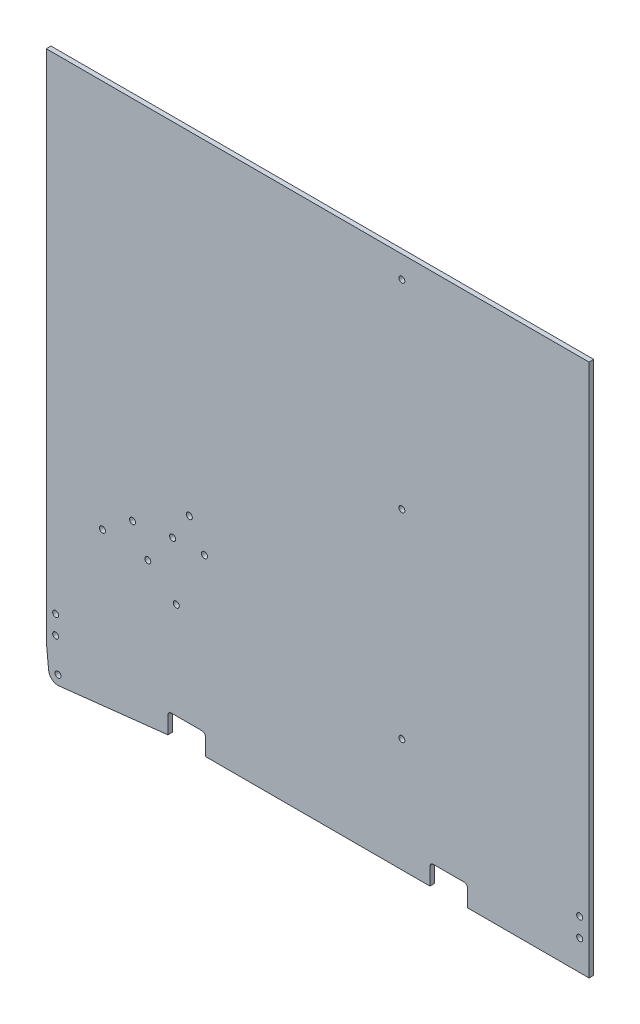
SolidWorks part; units mm, degrees
ref_plane "Front Plane" through (0, 0, 0) normal (0, 0, 1) x (1, 0, 0)
ref_plane "Top Plane" through (0, 0, 0) normal (0, 1, 0) x (1, 0, 0)
ref_plane "Right Plane" through (0, 0, 0) normal (1, 0, 0) x (0, 0, -1)
sketch "Sketch1" plane through (0, 0, 0) normal (0, 0, 1) x (1, 0, 0)
  line L0 (82.55, -20.32) -> (82.55, -6.35)
  line L2 (0, 0) -> (0, 341.63)
  line L3 (0, 341.63) -> (368.3, 341.63)
  line L4 (368.3, -20.32) -> (368.3, 341.63)
  line L5 (82.55, -6.35) -> (107.95, -6.35)
  line L6 (107.95, -6.35) -> (107.95, -20.32)
  line L7 (107.95, -20.32) -> (260.35, -20.32)
  line L8 (260.35, -20.32) -> (260.35, -6.35)
  line L9 (260.35, -6.35) -> (285.75, -6.35)
  line L10 (285.75, -6.35) -> (285.75, -20.32)
  line L11 (285.75, -20.32) -> (368.3, -20.32)
  line L12 (361.95, 12.7) -> (368.3, 12.7) construction
  line L13 (0, 0) -> (6.35, 0) construction
  line L14 (0.0315, -6.9818) -> (1.619, -22.8568)
  line L15 (8.6391, -28.5361) -> (82.55, -20.32)
  line L16 (0, 0) -> (0, -6.35)
  line L17 (85.725, 97.155) -> (82.9754, 95.5675) construction
  line L18 (97.0634, 115.6163) -> (58.5686, 93.3913) construction
  line L19 (97.0634, 115.6163) -> (107.3822, 97.7437) construction
  line L20 (58.5686, 93.3913) -> (68.8873, 75.5187) construction
  line L21 (107.3822, 97.7437) -> (68.8873, 75.5187) construction
  line L22 (97.0634, 115.6163) -> (68.8873, 75.5187) construction
  line L23 (58.5686, 93.3913) -> (107.3822, 97.7437) construction
  line L24 (7.9375, -22.225) -> (88.2169, 59.1366) construction
  line L25 (241.3, 56.63) -> (241.3, 191.63) construction
  line L26 (241.3, 191.63) -> (241.3, 326.63) construction
  circle A0 centre (6.35, 0) radius 2.032
  circle A1 centre (6.35, 12.7) radius 2.032
  circle A2 centre (361.95, 0) radius 2.032
  circle A3 centre (361.95, 12.7) radius 2.032
  arc A5 (1.619, -22.8568) -> (8.6391, -28.5361) centre (7.9375, -22.225) ccw
  circle A6 centre (7.9375, -22.225) radius 2.032
  arc A7 (0, -6.35) -> (0.0315, -6.9818) centre (6.35, -6.35) ccw
  circle A8 centre (38.1, 78.105) radius 2.032
  circle A9 centre (85.725, 97.155) radius 2.032
  circle A10 centre (58.5686, 93.3913) radius 2.032
  circle A11 centre (68.8873, 75.5187) radius 2.032
  circle A12 centre (107.3822, 97.7437) radius 2.032
  circle A13 centre (97.0634, 115.6163) radius 2.032
  circle A14 centre (88.2169, 59.1366) radius 2.032
  circle A15 centre (241.3, 56.63) radius 2
  circle A16 centre (241.3, 191.63) radius 2
  circle A17 centre (241.3, 326.63) radius 2
  point P46 (248.5125, 293.4319)
  dimension "D6" = 4.064
  dimension "D10" = 6.35
  dimension "D11" = 4.064
  dimension "D17" = 38.1
  dimension "D27" = 4
  dimension "D2" = 361.95
  dimension "D3" = 13.97
  dimension "D4" = 25.4
  dimension "D5" = 152.4
  dimension "D7" = 12.7
  dimension "D8" = 6.35
  dimension "D9" = 20.32
  dimension "D12" = 22.225
  dimension "D13" = 1.5875
  dimension "D14" = 82.55
  dimension "D15" = 368.3
  dimension "D16" = 6.35
  dimension "D18" = 98.425
  dimension "D19" = 47.625
  dimension "D20" = 19.05
  dimension "D21" = 3.175
  dimension "D22" = 60
  dimension "D23" = 20.6375
  dimension "D24" = 44.45
  dimension "D25" = 38.1
  dimension "D26" = 114.3
  dimension "D28" = 135
  dimension "D29" = 15
  dimension "D30" = 127
extrude "Boss-Extrude1" add sketch "Sketch1" along normal blind 3.175
fillet "Fillet1" radius 2.286 4 edges at (285.75, -6.35, 1.5875) (107.95, -6.35, 1.5875) (260.35, -6.35, 1.5875) (82.55, -6.35, 1.5875)
